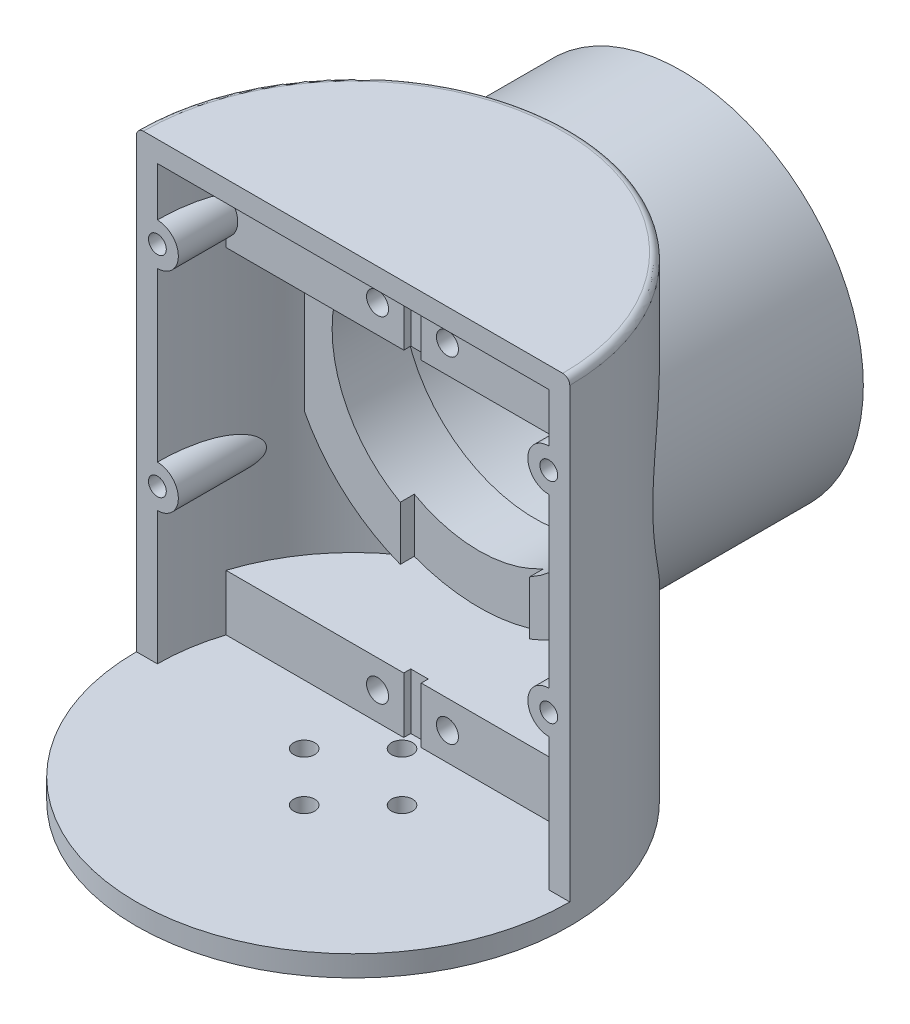
SolidWorks part; units mm, degrees
material "ABS"
ref_plane "Спереди" through (0, 0, 0) normal (0, 0, 1) x (1, 0, 0)
ref_plane "Сверху" through (0, 0, 0) normal (0, 1, 0) x (1, 0, 0)
ref_plane "Справа" through (0, 0, 0) normal (1, 0, 0) x (0, 0, -1)
sketch "Эскиз3" plane through (0, 0, 0) normal (1, 0, 0) x (0, 0, -1)
  line L0 (0, 68.2882) -> (0, 0) construction
  line L1 (0, 0) -> (31, 0)
  line L2 (31, 0) -> (31, 68)
  line L3 (31, 68) -> (0, 68)
  line L4 (0, 68) -> (0, 65)
  line L5 (0, 65) -> (28, 65)
  line L6 (28, 65) -> (28, 3)
  line L7 (28, 3) -> (0, 3)
  line L8 (0, 3) -> (0, 0)
  dimension "D1" = 62
  dimension "D2" = 68
  dimension "D3" = 3
  dimension "D4" = 3
  dimension "D5" = 3
revolve "Повернуть2" add sketch "Эскиз3" angle 360 about L0
sketch "Эскиз4" plane through (0, 68, 0) normal (0, 1, 0) x (1, 0, 0)
  line L0 (-31, 0) -> (31, 0)
  circle A0 centre (0, 0) radius 31 construction
  arc A1 (31, 0) -> (-31, 0) centre (0, 0) cw
extrude "Вырез-Вытянуть1" cut sketch "Эскиз4" against normal blind 65
sketch "Эскиз6" plane through (0, 0, 0) normal (0, -1, 0) x (1, 0, 0)
  circle A0 centre (7, 0) radius 1.5
  dimension "D1" = 3
  dimension "D2" = 7
extrude "Вырез-Вытянуть3" cut sketch "Эскиз6" against normal up to surface (3 mm away) up to face at (0, 3, 0.75)
pattern_circular "Круговой массив1" count 4 over 360 about axis through (0, 68.2882, 0) along (0, 1, 0) of "Вырез-Вытянуть3"
sketch "Эскиз7" plane through (0, 0, 0) normal (0, 0, 1) x (1, 0, 0)
  circle A0 centre (0, 41) radius 21
  circle A1 centre (0, 41) radius 26
  dimension "D1" = 52
  dimension "D2" = 42
  dimension "D3" = 41
extrude "Бобышка-Вытянуть1" add sketch "Эскиз7" against normal blind 31 from offset 16 offset against normal yes
sketch "Эскиз22" plane through (0, 0, -16) normal (0, 0, 1) x (1, 0, 0)
  line L0 (28, 3) -> (-28, 3) construction
  line L1 (-22.9783, 65) -> (22.9783, 65)
  line L2 (-22.9783, 65) -> (-22.9783, 51)
  line L3 (-22.9783, 51) -> (22.9783, 51)
  line L4 (22.9783, 65) -> (22.9783, 51)
  line L5 (-22.9783, 3) -> (22.9783, 3)
  line L6 (-28, 65) -> (-10, 65) construction
  line L7 (-22.9783, 28.8345) -> (-22.9783, 53.1655) construction
  line L8 (22.9783, 53.1655) -> (22.9783, 28.8345) construction
  line L9 (-22.9783, 3) -> (-22.9783, 11)
  line L10 (-22.9783, 11) -> (22.9783, 11)
  line L11 (22.9783, 3) -> (22.9783, 11)
  dimension "D1" = 14
  dimension "D2" = 8
extrude "Бобышка-Вытянуть7" add sketch "Эскиз22" against normal up to surface (7.5 mm away) from offset 7.5 up to face at (0.3812, 42.067, -16.5146)
sketch "Эскиз8" plane through (0, 0, -47) normal (0, 0, -1) x (-1, 0, 0)
  circle A0 centre (0, 41) radius 21
  dimension "D1" = 42
  dimension "D2" = 41
extrude "Вырез-Вытянуть4" cut sketch "Эскиз8" against normal up to surface (31 mm away) up to face at (0, 36.1391, -16)
sketch "Эскиз11" plane through (0, 0, 0) normal (0, 0, 1) x (1, 0, 0)
  line L0 (-28, 65) -> (-28, 3) construction
  line L1 (28, 3) -> (28, 65) construction
  line L3 (-28, 25) -> (28, 25) construction
  line L4 (-28, 25) -> (-28, 55) construction
  line L5 (-28, 55) -> (28, 55) construction
  line L6 (28, 25) -> (28, 55) construction
  circle A0 centre (-28, 55) radius 3
  circle A1 centre (-28, 25) radius 3
  circle A2 centre (28, 25) radius 3
  circle A3 centre (28, 55) radius 3
  point P12 (0, 25)
  point P15 (28, 40)
  dimension "D1" = 6
  dimension "D2" = 6
  dimension "D3" = 6
  dimension "D4" = 6
  dimension "D5" = 30
  dimension "D6" = 40
extrude "Бобышка-Вытянуть3" add sketch "Эскиз11" against normal up to surface (12.6095 mm away) up to face at (0.2009, 31.4276, -13.2427)
hole_wizard "Сверло под метчик  спиральное M2.52" positions "Эскиз15" profile "Эскиз16" hole size "M2.5x0.45" standard "Ansi Metric"
sketch "Эскиз15" plane through (0, 0, 0) normal (0, 0, 1) x (1, 0, 0)
  point P0 (-28, 55)
  point P3 (28, 55)
  point P6 (28, 25)
  point P9 (-28, 25)
sketch "Эскиз16" plane through (-28, 55, 0) normal (1, 0, 0) x (0, -1, 0)
  line L0 (0, 0) -> (0, 5.7661)
  line L1 (0, 5.7661) -> (1.275, 5)
  line L2 (1.275, 5) -> (1.275, 0)
  line L5 (1.275, 0) -> (0, 0)
  line L10 (0, 5.7661) -> (-1.275, 5) construction
  line L11 (0, -6.35) -> (0, 107.95) construction
  dimension "Диаметр отверстия" = 2.55
  dimension "Глубина отверстия" = 5
  dimension "Угол заточки сверла" = 118
hole_wizard "Отверстие обработанное метчиком M21" positions "Эскиз18" profile "Эскиз19" tap size "M2" standard "DIN"
sketch "Эскиз18" plane through (0, 0, -47) normal (0, 0, -1) x (-1, 0, 0)
  line L2 (0, 41) -> (23, 41) construction
  line L4 (0, 41) -> (16.2635, 57.2635) construction
  circle A1 centre (0, 41) radius 23 construction
  point P0 (16.2635, 57.2635)
  dimension "D1" = 46
  dimension "D2" = 45
cosmetic thread "Отверстие резьбы1" parameters "D1"=8, "D2"=2
sketch "Эскиз19" plane through (-16.2635, 57.2635, -47) normal (1, 0, 0) x (0, 1, 0)
  line L0 (0, 0) -> (0, 10.4807)
  line L1 (0, 10.4807) -> (0.8, 10)
  line L2 (0.8, 10) -> (0.8, 0.225)
  line L3 (0.8, 0.225) -> (1.025, 0)
  line L5 (1.025, 0) -> (0, 0)
  line L6 (-0.8, 0.225) -> (-1.025, 0) construction
  line L10 (0, 10.4807) -> (-0.8, 10) construction
  line L11 (0, -6.35) -> (0, 107.95) construction
  dimension "Диаметр сверла" = 1.6
  dimension "Глубина сверла" = 10
  dimension "Диаметр передней зенковки" = 2.05
  dimension "Угол передней зенковки" = 90
  dimension "Угол заточки сверла" = 118
pattern_circular "Круговой массив2" count 8 over 360 about axis through (0, 41, -47) along (0, 0, 1) of "Отверстие обработанное метчиком M21"
ref_plane "Плоскость1" through (0, 0, -26) normal (0, 0, -1) x (-1, 0, 0)
sketch "Эскиз20" plane through (0, 0, -26) normal (0, 0, -1) x (-1, 0, 0)
  circle A0 centre (0, 41) radius 19
  circle A1 centre (0, 41) radius 26
  dimension "D1" = 38
  dimension "D2" = 52
extrude "Бобышка-Вытянуть6" add sketch "Эскиз20" against normal blind 10 contours A1 A0 region at (25.2646, 41, -26)
fillet "Скругление1" radius 1 1 edges at (0, 68, -31)
sketch "Эскиз23" plane through (-22.9783, 0, 0) normal (-1, 0, 0) x (0, 0, 1)
  line L1 (-16, 65) -> (-8.5, 65)
  line L2 (-16, 65) -> (-16, 51)
  line L3 (-16, 51) -> (-8.5, 51)
  line L4 (-8.5, 65) -> (-8.5, 51)
  line L5 (-16, 11) -> (-8.5, 11)
  line L6 (-16, 11) -> (-16, 3)
  line L7 (-16, 3) -> (-8.5, 3)
  line L8 (-8.5, 11) -> (-8.5, 3)
extrude "Бобышка-Вытянуть8" add sketch "Эскиз23" along normal up to next
mirror "Зеркальное отражение1" about plane through (0, 0, 0) normal (1, 0, 0) of "Бобышка-Вытянуть8"
sketch "Эскиз24" plane through (0, 0, -8.5) normal (0, 0, 1) x (1, 0, 0)
  line L0 (0, 51) -> (0, 66.3483) construction
  line L1 (-26.6786, 51) -> (26.6786, 51) construction
  line L2 (1.25, 51) -> (-1.25, 51)
  line L3 (-1.25, 51) -> (-1.25, 65)
  line L4 (-1.25, 65) -> (1.25, 65)
  line L5 (28, 65) -> (-28, 65) construction
  line L6 (1.25, 51) -> (1.25, 65)
  line L7 (1.25, 3) -> (-1.25, 3)
  line L8 (-26.6786, 3) -> (0, 3) construction
  line L9 (-1.25, 3) -> (-1.25, 11)
  line L10 (26.6786, 11) -> (-26.6786, 11) construction
  line L11 (-1.25, 11) -> (1.25, 11)
  line L12 (1.25, 3) -> (1.25, 11)
  point P14 (0, 65)
  point P23 (0, 11)
  point P24 (0, 3)
  dimension "D1" = 2.5
extrude "Вырез-Вытянуть5" cut sketch "Эскиз24" against normal blind 1
hole_wizard "Сверло под метчик  спиральное M31" positions "Эскиз25" profile "Эскиз26" hole size "M3x0.5" standard "Ansi Metric"
sketch "Эскиз25" plane through (0, 0, -8.5) normal (0, 0, 1) x (1, 0, 0)
  line L0 (-26.6786, 51) -> (-1.25, 51) construction
  line L1 (-1.25, 51) -> (1.25, 51) construction
  line L3 (-1.25, 11) -> (-26.6786, 11) construction
  line L4 (1.25, 11) -> (-1.25, 11) construction
  point P0 (-5, 55)
  point P2 (5, 55)
  point P9 (0, 51)
  point P13 (-5, 7)
  point P15 (5, 7)
  point P25 (0, 11)
  dimension "D1" = 10
  dimension "D2" = 4
  dimension "D3" = 5
  dimension "D4" = 10
  dimension "D5" = 4
  dimension "D6" = 5
sketch "Эскиз26" plane through (-5, 55, -8.5) normal (1, 0, 0) x (0, -1, 0)
  line L0 (0, 0) -> (0, 10.9464)
  line L1 (0, 10.9464) -> (1.575, 10)
  line L2 (1.575, 10) -> (1.575, 0)
  line L5 (1.575, 0) -> (0, 0)
  line L10 (0, 10.9464) -> (-1.575, 10) construction
  line L11 (0, -6.35) -> (0, 107.95) construction
  dimension "Диаметр отверстия" = 3.15
  dimension "Глубина отверстия" = 10
  dimension "Угол заточки сверла" = 118
sketch "Эскиз30" plane through (0, 0, -16) normal (0, 0, 1) x (1, 0, 0)
  line L0 (0, 33.5115) -> (0, 8.4107) construction
  line L1 (-9.25, 24.4037) -> (-9.25, 16.7011)
  line L2 (9.25, 24.4037) -> (9.25, 16.7011)
  arc A0 (-16.1555, 51) -> (16.1555, 51) centre (0, 41) ccw construction
  arc A1 (-22.9783, 28.8345) -> (22.9783, 28.8345) centre (0, 41) ccw construction
  arc A2 (9.25, 24.4037) -> (-9.25, 24.4037) centre (0, 41) cw
  arc A3 (9.25, 16.7011) -> (-9.25, 16.7011) centre (0, 41) cw
  dimension "D1" = 18.5
extrude "Вырез-Вытянуть6" cut sketch "Эскиз30" against normal blind 2
